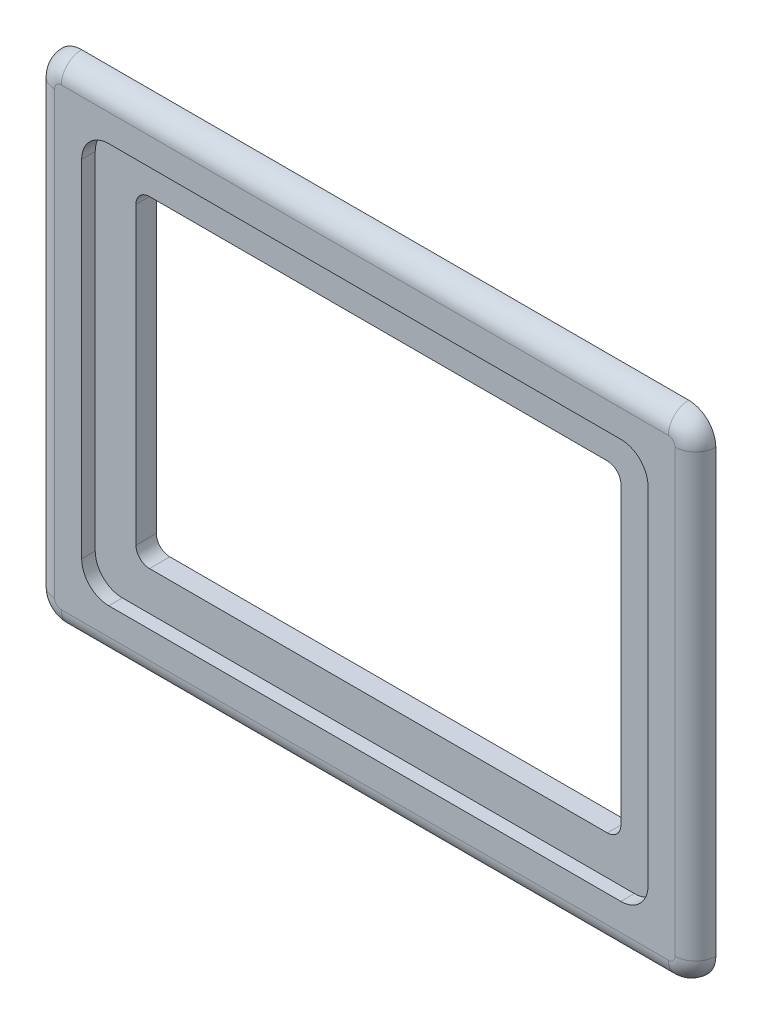
SolidWorks part; units mm, degrees
material "ABS"
ref_plane "Front Plane" through (0, 0, 0) normal (0, 0, 1) x (1, 0, 0)
ref_plane "Top Plane" through (0, 0, 0) normal (0, 1, 0) x (1, 0, 0)
ref_plane "Right Plane" through (0, 0, 0) normal (1, 0, 0) x (0, 0, -1)
sketch "Sketch1" plane through (0, 0, 0) normal (0, 0, 1) x (1, 0, 0)
  line L1 (-154.7812, -115.8875) -> (154.7812, -115.8875)
  line L2 (-154.7812, -115.8875) -> (-154.7812, 115.8875)
  line L3 (-154.7812, 115.8875) -> (154.7812, 115.8875)
  line L4 (154.7812, -115.8875) -> (154.7812, 115.8875)
  line L5 (-154.7812, -115.8875) -> (154.7812, 115.8875) construction
  line L6 (-154.7812, 115.8875) -> (154.7812, -115.8875) construction
  line L11 (-100.7138, -75.4062) -> (100.7138, 75.4063) construction
  line L12 (-100.7138, 75.4063) -> (100.7138, -75.4062) construction
  line L13 (-113.5063, -75.4063) -> (113.5062, -75.4063)
  line L14 (-113.5063, -75.4063) -> (-113.5063, 75.4062)
  line L15 (-113.5063, 75.4062) -> (113.5062, 75.4062)
  line L16 (113.5062, -75.4063) -> (113.5062, 75.4062)
  line L17 (-113.5063, -75.4063) -> (113.5062, 75.4062) construction
  line L18 (-113.5063, 75.4062) -> (113.5062, -75.4063) construction
  line L19 (-132.5562, -93.6625) -> (132.5562, -93.6625)
  line L20 (-132.5562, -93.6625) -> (-132.5562, 93.6625)
  line L21 (-132.5562, 93.6625) -> (132.5562, 93.6625)
  line L22 (132.5562, -93.6625) -> (132.5562, 93.6625)
  line L23 (-132.5562, -93.6625) -> (132.5562, 93.6625) construction
  line L24 (-132.5562, 93.6625) -> (132.5562, -93.6625) construction
  point P0 (0, 0)
  point P6 (0, 0)
  point P11 (0, 0)
  point P16 (0, 0)
  dimension "D1" = 309.5625
  dimension "D2" = 231.775
  dimension "D3" = 227.0125
  dimension "D4" = 150.8125
  dimension "D5" = 265.1125
  dimension "D6" = 187.325
extrude "Boss-Extrude1" add sketch "Sketch1" along normal blind 9.525 contours L1 L4 L3 L2 L22 L19 L20 L21 | L19 L22 L21 L20 L16 L13 L14 L15 region at (-150.9141, 0, 0) region at (-129.3101, 0, 0)
extrude "Boss-Extrude2" add sketch "Sketch1<3>" against normal blind 6.35 contours L19 L22 L21 L20 L16 L13 L14 L15 region at (-129.3101, 0, 0)
sketch "Sketch1<3>" plane through (0, 0, 0) normal (0, 0, 1) x (1, 0, 0) same geometry as "Sketch1"
fillet "Fillet1" radius 12.7 8 edges at (132.5562, -93.6625, -3.175) (132.5562, 93.6625, -3.175) (-132.5562, 93.6625, -3.175) (-132.5562, -93.6625, -3.175) (154.7812, 115.8875, 4.7625) (154.7812, -115.8875, 4.7625) (-154.7812, 115.8875, 4.7625) (-154.7812, -115.8875, 4.7625)
extrude "Cut-Extrude1" cut sketch "Sketch1<4>" along direction (0, 0, 1) on the side against the normal blind 6.35 from surface contours L19 L22 L21 L20 L16 L13 L14 L15 region at (-129.3101, 0, 0) starting at face at (0, 0, 9.525)
sketch "Sketch1<4>" plane through (0, 0, 0) normal (0, 0, 1) x (1, 0, 0) same geometry as "Sketch1"
fillet "Fillet2" radius 6.35 4 edges at (113.5062, -75.4063, -1.5875) (-113.5063, -75.4063, -1.5875) (113.5062, 75.4062, -1.5875) (-113.5063, 75.4062, -1.5875)
fillet "Fillet3" radius 12.7 4 edges at (132.5562, 93.6625, 6.35) (132.5562, -93.6625, 6.35) (-132.5562, -93.6625, 6.35) (-132.5562, 93.6625, 6.35)
fillet "Fillet4" radius 9.525 8 edges at (-151.0615, -112.1678, 9.525) (0, -115.8875, 9.525) (151.0615, -112.1678, 9.525) (154.7812, 0, 9.525) (151.0615, 112.1678, 9.525) (0, 115.8875, 9.525) (-151.0615, 112.1678, 9.525) (-154.7812, 0, 9.525)
